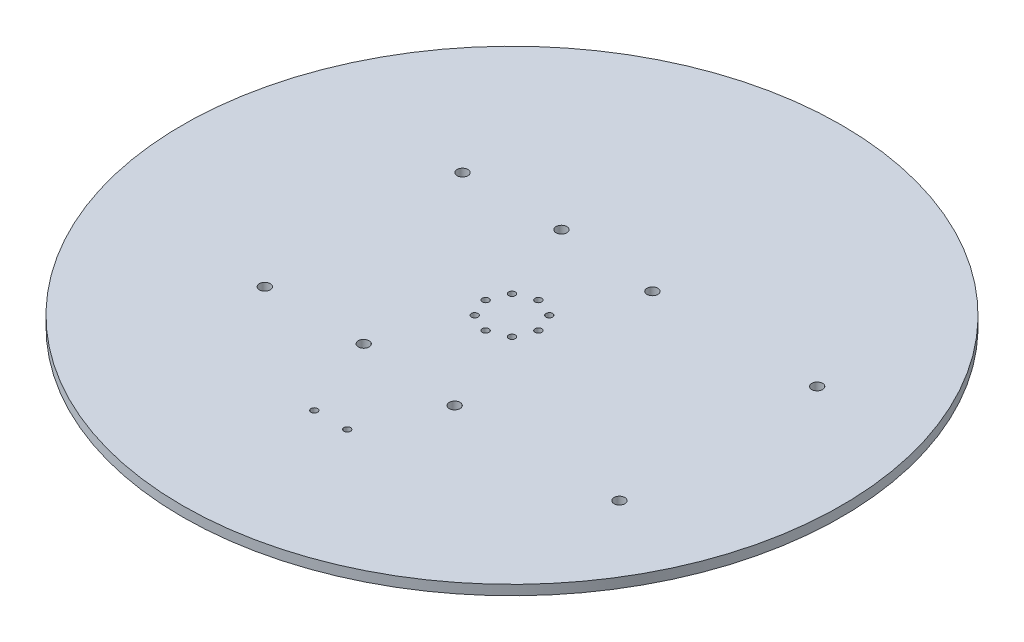
SolidWorks part; units mm, degrees
material "ABS"
ref_plane "Front Plane" through (0, 0, 0) normal (0, 0, 1) x (1, 0, 0)
ref_plane "Top Plane" through (0, 0, 0) normal (0, 1, 0) x (1, 0, 0)
ref_plane "Right Plane" through (0, 0, 0) normal (1, 0, 0) x (0, 0, -1)
sketch "Sketch2" plane through (0, 0, 0) normal (0, 1, 0) x (1, 0, 0)
  circle A0 centre (0, 0) radius 100
  dimension "D1" = 200
extrude "Boss-Extrude1" add sketch "Sketch2" along normal blind 3
sketch "Sketch3" plane through (0, 0, 0) normal (0, -1, 0) x (1, 0, 0)
  circle A0 centre (0, 75) radius 7.5
  dimension "D1" = 75
  dimension "D2" = 15
extrude "Boss-Extrude2" add sketch "Sketch3" along normal blind 4.75
sketch "Sketch4" plane through (0, 0, 0) normal (0, 0, 1) x (1, 0, 0)
  line L0 (0, 3) -> (0, -49997) construction
  line L1 (100, 3) -> (-100, 3) construction
  point P4 (0, 3)
pattern_circular "CirPattern1" count 5 over 360 about axis through (0, 3, 0) along (0, -1, 0) of "Boss-Extrude2"
fillet "Fillet3" radius 8 5 edges at (0, -4.75, 67.5) (64.1963, -4.75, 20.8586) (39.6755, -4.75, -54.6086) (-39.6755, -4.75, -54.6086) (-64.1963, -4.75, 20.8586)
sketch "Sketch5" plane through (0, 0, 0) normal (0, -1, 0) x (1, 0, 0)
  line L1 (-0.75, -9.5) -> (0.75, -9.5)
  line L2 (-0.75, -9.5) -> (-0.75, -12.5)
  line L3 (-0.75, -12.5) -> (0.75, -12.5)
  line L4 (0.75, -9.5) -> (0.75, -12.5)
  line L5 (-0.75, -9.5) -> (0.75, -12.5) construction
  line L6 (-0.75, -12.5) -> (0.75, -9.5) construction
  circle A0 centre (0, 0) radius 11
  circle A1 centre (0, 8) radius 1
  circle A2 centre (5.6569, 5.6569) radius 1
  circle A3 centre (8, 0) radius 1
  circle A4 centre (5.6569, -5.6569) radius 1
  circle A5 centre (0, -8) radius 1
  circle A6 centre (-5.6569, -5.6569) radius 1
  circle A7 centre (-8, 0) radius 1
  circle A8 centre (-5.6569, 5.6569) radius 1
  point P5 (0, -11)
  point P22 (0, 0)
  dimension "D1" = 22
  dimension "D2" = 2
  dimension "D3" = 8
  dimension "D5" = 8
  dimension "D6" = 1.5
  dimension "D7" = 3
  dimension "D4" = 8
extrude "Cut-Extrude1" cut sketch "Sketch5" against normal up to surface (3 mm away) contours A8 | A1 | A2 | A3 | A4 | A5 | A6 | A7 up to face at (0, 3, 100)
extrude "Boss-Extrude3" add sketch "Sketch5<3>" along normal blind 3 contours L2 A0 L4 L1 | A0 L2 L3 L4 region at (0, 0, -10.2458) region at (0, 0, -11.7457)
sketch "Sketch5<3>" plane through (0, 0, 0) normal (0, -1, 0) x (1, 0, 0) same geometry as "Sketch5"
sketch "Sketch6" plane through (0, 3, 0) normal (0, 1, 0) x (1, 0, 0)
  line L1 (-45, 30) -> (-15, 30)
  line L2 (-45, 30) -> (-45, -30)
  line L3 (-45, -30) -> (-15, -30)
  line L4 (-15, 30) -> (-15, -30)
  circle A0 centre (-45, 30) radius 2
  circle A1 centre (-15, 30) radius 2
  circle A2 centre (-15, -30) radius 2
  circle A3 centre (-45, -30) radius 2
  point P4 (-15, 0)
  dimension "D4" = 4
  dimension "D1" = 30
  dimension "D2" = 60
  dimension "D3" = 15
  dimension "D5" = 2
  dimension "D6" = 2
hole_wizard "Tap Drill for M4x0.7 Tap1" positions "3DSketch1" profile "Sketch7" hole size "M4x0.7" standard "ANSI Metric" end condition up to next
sketch3d "3DSketch1"
  point P0 (-45, 3, -30)
  point P3 (-15, 3, -30)
  point P6 (-45, 3, 30)
  point P9 (-15, 3, 30)
sketch "Sketch7" plane through (-45, 3, -30) normal (1, 0, 0) x (0, 0, 1)
  line L0 (0, 0) -> (0, 3)
  line L1 (0, 3) -> (1.65, 3)
  line L2 (1.65, 3) -> (1.65, 0)
  line L5 (1.65, 0) -> (0, 0)
  line L11 (0, -6.35) -> (0, 107.95) construction
  dimension "Thru Hole Dia." = 3.3
  dimension "Thru Hole Depth" = 3
sketch "Sketch8" plane through (0, 3, 0) normal (0, 1, 0) x (1, 0, 0)
  line L5 (-15, 30) -> (-15, -30) construction
  line L7 (15, 27.6) -> (65, 27.6)
  line L8 (15, 27.6) -> (15, -32.4)
  line L9 (15, -32.4) -> (65, -32.4)
  line L10 (65, 27.6) -> (65, -32.4)
  line L13 (-45, 30) -> (-15, 30) construction
  line L14 (13.9, -16) -> (65, -16)
  line L15 (13.9, -13.75) -> (13.9, -18.25) construction
  circle A0 centre (15, 27.6) radius 2
  circle A1 centre (65, 27.6) radius 2
  circle A2 centre (15, -32.4) radius 2
  circle A3 centre (65, -32.4) radius 2
  dimension "D4" = 4
  dimension "D5" = 4
  dimension "D6" = 4
  dimension "D7" = 4
  dimension "D1" = 50
  dimension "D2" = 60
  dimension "D3" = 30
  dimension "D8" = 2.4
  dimension "D9" = 2.9021
hole_wizard "Tap Drill for M4x0.7 Tap2" positions "3DSketch2" profile "Sketch9" hole size "M4x0.7" standard "ANSI Metric" end condition up to next
sketch3d "3DSketch2"
  point P0 (15, 3, -27.6)
  point P3 (15, 3, 32.4)
  point P6 (65, 3, 32.4)
  point P9 (65, 3, -27.6)
sketch "Sketch9" plane through (15, 3, -27.6) normal (1, 0, 0) x (0, 0, 1)
  line L0 (0, 0) -> (0, 3)
  line L1 (0, 3) -> (1.65, 3)
  line L2 (1.65, 3) -> (1.65, 0)
  line L5 (1.65, 0) -> (0, 0)
  line L11 (0, -6.35) -> (0, 107.95) construction
  dimension "Thru Hole Dia." = 3.3
  dimension "Thru Hole Depth" = 3
sketch "Sketch10" plane through (0, 3, 0) normal (0, 1, 0) x (1, 0, 0)
  line L0 (0, 0) -> (0, 100) construction
  line L1 (-5, -55) -> (5, -55)
  line L2 (-5, -55) -> (-5, -65)
  line L3 (-5, -65) -> (5, -65)
  line L4 (5, -55) -> (5, -65)
  line L5 (0, -55) -> (0, -65) construction
  circle A0 centre (-5, -65) radius 1
  circle A1 centre (5, -65) radius 1
  circle A2 centre (5, -55) radius 1
  circle A3 centre (-5, -55) radius 1
  circle A4 centre (0, 0) radius 100 construction
  dimension "D3" = 2
  dimension "D4" = 2
  dimension "D5" = 2
  dimension "D6" = 2
  dimension "D1" = 10
  dimension "D2" = 10
  dimension "D7" = 65
extrude "Cut-Extrude2" cut sketch "Sketch10" against normal through all contours A3 | A2
